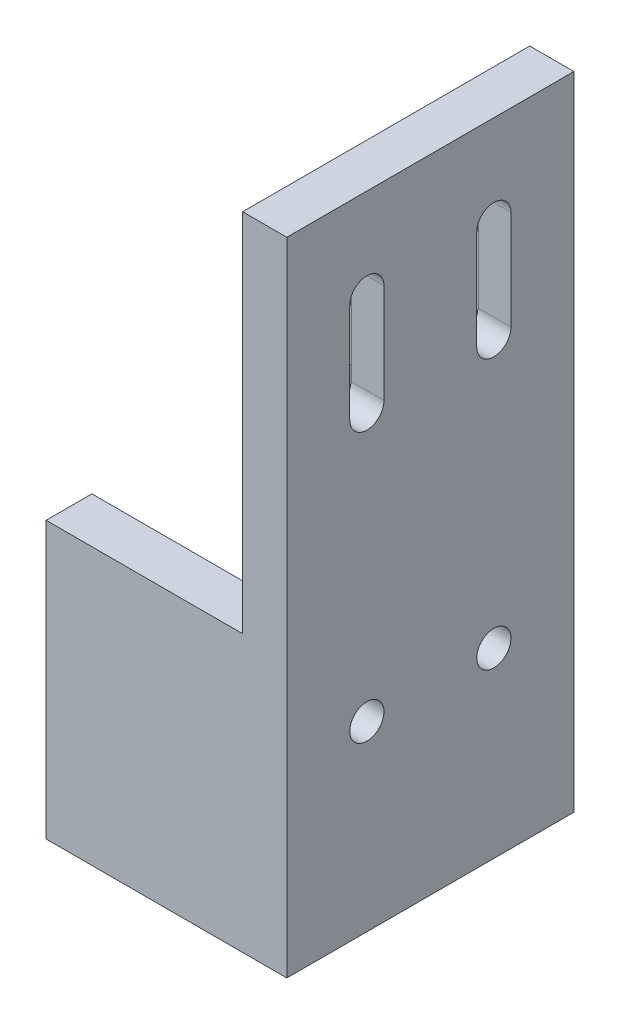
SolidWorks part; units mm, degrees
ref_plane "Front Plane" through (0, 0, 0) normal (0, 0, 1) x (1, 0, 0)
ref_plane "Top Plane" through (0, 0, 0) normal (0, 1, 0) x (1, 0, 0)
ref_plane "Right Plane" through (0, 0, 0) normal (1, 0, 0) x (0, 0, -1)
sketch "ProfileSketch1" plane through (0, 0, 0) normal (0, 0, 1) x (1, 0, 0)
  line L0 (0, 0) -> (4, 0)
  line L1 (4, 0) -> (4, 58.1)
  line L2 (4, 58.1) -> (0, 58.1)
  line L3 (0, 58.1) -> (0, 0)
  dimension "D1" = 58.1
  dimension "D4" = 4
extrude "Boss-Extrude1" add sketch "ProfileSketch1" along normal blind 26
sketch "ProbeSlidingMountSketch4" plane through (0, 0, 0) normal (-1, 0, 0) x (0, 0, 1)
  line L0 (26, 58.1) -> (0, 58.1) construction
  line L3 (5.7, 49.9) -> (5.7, 40.9)
  line L4 (8.8, 49.9) -> (8.8, 40.9)
  line L5 (17.2, 49.9) -> (17.2, 40.9)
  line L6 (20.3, 49.9) -> (20.3, 40.9)
  line L7 (0, 58.1) -> (0, 0) construction
  line L8 (26, 0) -> (0, 0) construction
  line L9 (26, 58.1) -> (26, 0) construction
  arc A0 (8.8, 49.9) -> (5.7, 49.9) centre (7.25, 49.9) ccw
  arc A1 (5.7, 40.9) -> (8.8, 40.9) centre (7.25, 40.9) ccw
  arc A2 (20.3, 49.9) -> (17.2, 49.9) centre (18.75, 49.9) ccw
  arc A3 (17.2, 40.9) -> (20.3, 40.9) centre (18.75, 40.9) ccw
  circle A4 centre (7.25, 16.5) radius 1.55
  circle A5 centre (18.75, 16.5) radius 1.55
  dimension "D1" = 3.1
  dimension "D6" = 3.1
  dimension "D2" = 9
  dimension "D7" = 24.4
  dimension "D3" = 17.2
  dimension "D8" = 40.9
  dimension "D4" = 11.5
  dimension "D5" = 7.25
  dimension "D9" = 7.25
extrude "ProbeSlidingMountCut-Extrude3" cut sketch "ProbeSlidingMountSketch4" against normal through all
sketch "ProbeSlidingMountChannelSketch5" plane through (0, 0, 0) normal (-1, 0, 0) x (0, 0, 1)
  line L0 (7.25, 49.9) -> (7.25, 40.9) construction
  line L1 (10.45, 49.9) -> (10.45, 40.9)
  line L2 (4.05, 49.9) -> (4.05, 40.9)
  line L3 (18.75, 49.9) -> (18.75, 40.9) construction
  line L4 (21.95, 49.9) -> (21.95, 40.9)
  line L5 (15.55, 49.9) -> (15.55, 40.9)
  arc A0 (10.45, 49.9) -> (4.05, 49.9) centre (7.25, 49.9) ccw
  arc A1 (4.05, 40.9) -> (10.45, 40.9) centre (7.25, 40.9) ccw
  arc A2 (21.95, 49.9) -> (15.55, 49.9) centre (18.75, 49.9) ccw
  arc A3 (15.55, 40.9) -> (21.95, 40.9) centre (18.75, 40.9) ccw
  point P4 (7.25, 45.4)
  point P9 (18.75, 45.4)
  dimension "D1" = 6.4
extrude "ProbeSlidingMountChanelCut-Extrude4" cut sketch "ProbeSlidingMountChannelSketch5" against normal blind 1
sketch "InductiveProbeHolderSketch1" plane through (0, 0, 0) normal (-1, 0, 0) x (0, 0, 1)
  line L1 (0, 0) -> (4.15, 0)
  line L2 (0, 0) -> (0, 25)
  line L3 (0, 25) -> (4.15, 25)
  line L4 (4.15, 0) -> (4.15, 25)
  line L5 (26, 0) -> (21.85, 0)
  line L6 (26, 0) -> (26, 25)
  line L7 (26, 25) -> (21.85, 25)
  line L8 (21.85, 0) -> (21.85, 25)
  dimension "D1" = 17.7
  dimension "D2" = 25
extrude "InductiveProbeHolderBoss-Extrude2" add sketch "InductiveProbeHolderSketch1" along normal blind 17.8
equation "\"ProbeMountHeight\"= \"ProbeMountDepth\" + \"ProbeMountUpperHeight\""
equation "\"D1@ProfileSketch1\"=\"ProbeMountHeight\" + 30mm"
equation "\"D1@Boss-Extrude1\"= \"ProbeBodyWidth\""
equation "\"ProbeBodyWidth\"= 26mm"
equation "\"ProbeMountUpperHeight\"= \"M3ScrewButtonHeadHeight\" * 2 + \"M3ScrewDiameter\" * 5 + \"M3ScrewButtonHeadHeight\" * 2"
equation "\"D4@ProfileSketch1\"=\"ProbeMountDepth\"+1mm"
equation "\"M3ScrewButtonHeadHeight\"= 2.4mm"
equation "\"D1@ProbeSlidingMountSketch4\" = \"M3ScrewDiameter\""
equation "\"D2@ProbeSlidingMountSketch4\" = 3mm * 3"
equation "\"M3ScrewDiameter\"= 3.1mm"
equation "\"ProbeMountDepth\"= 3mm"
equation "\"M3ScrewButtonHeadDiameter\"= 5.9mm"
equation "\"D1@ProbeSlidingMountChannelSketch5\"=\"M3ScrewButtonHeadDiameter\"+ .5mm"
equation "\"D7@ProbeSlidingMountSketch4\"=13.5+10.9"
equation "\"InductiveProbeWidth\"= 17.7mm"
equation "\"D1@InductiveProbeHolderSketch1\" = \"InductiveProbeWidth\""
equation "\"ProbeMountingHoleDistance\"= 11.5mm"
equation "\"D5@ProbeSlidingMountSketch4\"=(\"ProbeBodyWidth\" - \"ProbeMountingHoleDistance\")/2"
equation "\"InductiveProbeDistanceBetweenMountingHoles\" = 11.5mm"
equation "\"D4@ProbeSlidingMountSketch4\"=\"InductiveProbeDistanceBetweenMountingHoles\""
